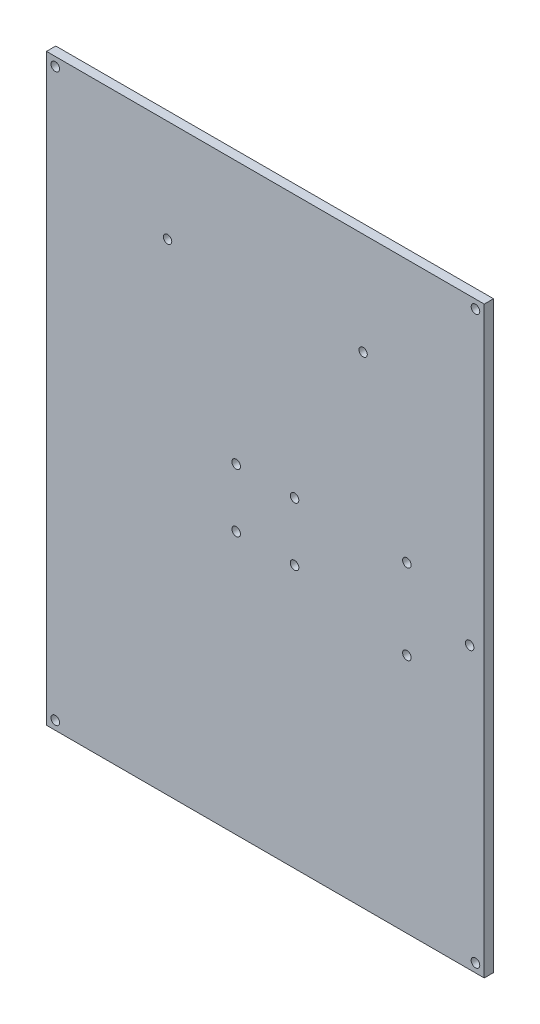
SolidWorks part; units mm, degrees
ref_plane "Front Plane" through (0, 0, 0) normal (0, 0, 1) x (1, 0, 0)
ref_plane "Top Plane" through (0, 0, 0) normal (0, 1, 0) x (1, 0, 0)
ref_plane "Right Plane" through (0, 0, 0) normal (1, 0, 0) x (0, 0, -1)
sketch "Sketch1" plane through (0, 0, 0) normal (0, 0, 1) x (1, 0, 0)
  line L1 (75, 100) -> (-75, 100)
  line L2 (75, 100) -> (75, -100)
  line L3 (75, -100) -> (-75, -100)
  line L4 (-75, 100) -> (-75, -100)
  line L5 (75, 100) -> (-75, -100) construction
  line L6 (75, -100) -> (-75, 100) construction
  point P0 (0, 0)
  dimension "D1" = 150
  dimension "D2" = 200
extrude "Boss-Extrude1" add sketch "Sketch1" along normal blind 3.18
sketch "Sketch2" plane through (0, 0, 3.18) normal (0, 0, 1) x (1, 0, 0)
  line L1 (60, -85) -> (90, -85)
  line L2 (60, -85) -> (60, -115)
  line L3 (60, -115) -> (90, -115)
  line L4 (90, -85) -> (90, -115)
  line L5 (60, -85) -> (90, -115) construction
  line L6 (60, -115) -> (90, -85) construction
  point P0 (75, -100)
  dimension "D1" = 30
extrude "Boss-Extrude2" [suppressed] add sketch "Sketch2" against normal blind 15
mirror "Mirror1" [suppressed] about plane through (0, 0, 0) normal (0, 1, 0)
mirror "Mirror2" [suppressed] about plane through (0, 0, 0) normal (1, 0, 0)
fillet "Fillet1" [suppressed] radius 3
sketch "Sketch4" plane through (0, 0, 3.18) normal (0, 0, 1) x (1, 0, 0)
  line L0 (-75, -100) -> (75, -100) construction
  line L1 (0, 0) -> (0, -100) construction
  circle A0 centre (10, -10) radius 1.47
  dimension "D1" = 2.94
  dimension "D2" = 10
  dimension "D4" = 10
extrude "Cut-Extrude2" cut sketch "Sketch4" against normal blind 10
mirror "Mirror3" about plane through (0, 0, 0) normal (1, 0, 0) of "Cut-Extrude2"
mirror "Mirror4" about plane through (0, 0, 0) normal (0, 1, 0) of "Mirror3"
ref_axis "Axis1" through (0, 0, -0.159) along (0, 0, 1)
sketch "Sketch5" plane through (0, 0, 3.18) normal (0, 0, 1) x (1, 0, 0)
  line L0 (-75, -100) -> (75, -100) construction
  line L1 (-75, 100) -> (-75, -100) construction
  circle A0 centre (-72, -97) radius 1.47
  dimension "D1" = 2.94
  dimension "D2" = 3
  dimension "D3" = 3
extrude "Cut-Extrude3" cut sketch "Sketch5" against normal blind 3.18
mirror "Mirror5" about plane through (0, 0, 0) normal (1, 0, 0) of "Cut-Extrude3"
mirror "Mirror6" about plane through (0, 0, 0) normal (0, 1, 0) of "Mirror5"
sketch "Sketch6" plane through (0, 0, 3.18) normal (0, 0, 1) x (1, 0, 0)
  line L0 (-75, -100) -> (75, -100) construction
  line L1 (0, 0) -> (0, -100) construction
  line L2 (75, 100) -> (-75, 100) construction
  circle A0 centre (33.5, 65) radius 1.425
  circle A1 centre (-33.5, 65) radius 1.425
  point P9 (0, 0)
  dimension "D1" = 2.85
  dimension "D2" = 67
  dimension "D3" = 35
extrude "Cut-Extrude5" cut sketch "Sketch6" against normal blind 3.18
sketch "Sketch7" plane through (0, 0, 3.18) normal (0, 0, 1) x (1, 0, 0)
  line L2 (75, -100) -> (75, 100) construction
  line L3 (75, 100) -> (-75, 100) construction
  circle A0 centre (70, -3.75) radius 1.47
  circle A1 centre (48.5, 10) radius 1.47
  circle A2 centre (48.5, -17.5) radius 1.47
  point P6 (60.7035, 25.7408)
  point P7 (40.2601, 25.7408)
  point P8 (52.126, 9.0046)
  point P9 (0, 0)
  point P10 (53.25, 19.3809)
  point P11 (0, 0)
  dimension "D1" = 2.94
  dimension "D2" = 27.5
  dimension "D4" = 5
  dimension "D5" = 90
  dimension "D3" = 21.5
  dimension "D6" = 103.75
extrude "Cut-Extrude6" cut sketch "Sketch7" against normal blind 3.18
